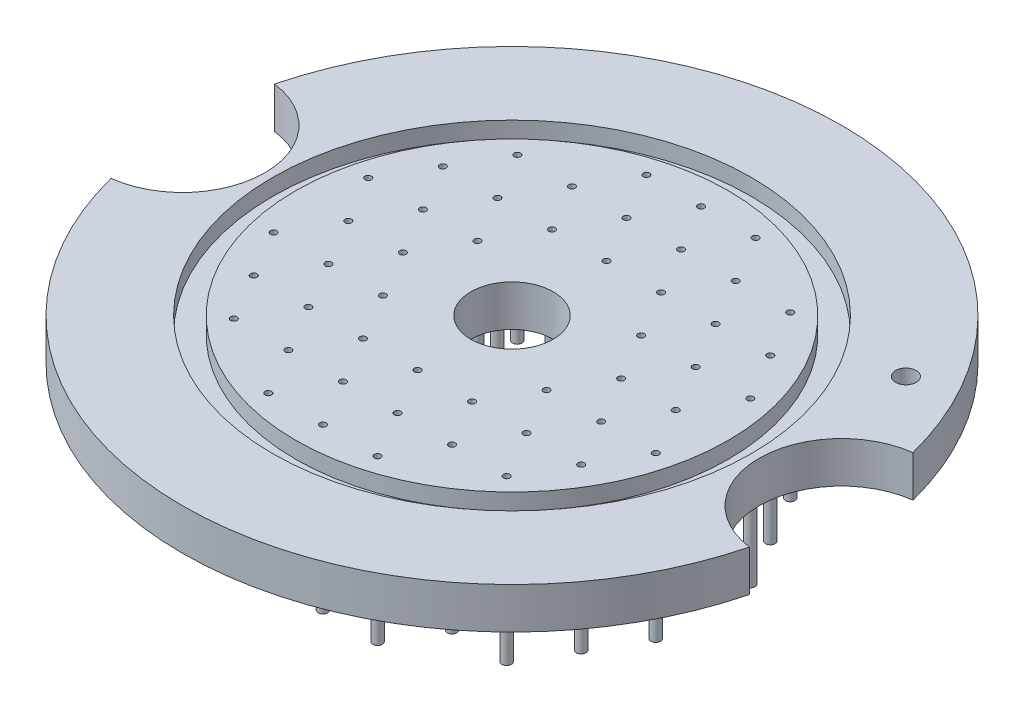
SolidWorks part; units mm, degrees
ref_plane "Front Plane" through (0, 0, 0) normal (0, 0, 1) x (1, 0, 0)
ref_plane "Top Plane" through (0, 0, 0) normal (0, 1, 0) x (1, 0, 0)
ref_plane "Right Plane" through (0, 0, 0) normal (1, 0, 0) x (0, 0, -1)
sketch "Sketch1" plane through (0, 0, 0) normal (0, 0, 1) x (1, 0, 0)
  line L0 (-33.3375, 6.35) -> (-33.3375, 3.81)
  line L1 (0, 0) -> (-50.8, 0)
  line L2 (0, 0) -> (0, 6.35)
  line L3 (0, 6.35) -> (-33.3375, 6.35)
  line L4 (-50.8, 0) -> (-50.8, 6.35)
  line L5 (-33.3375, 3.81) -> (-36.8935, 3.81)
  line L6 (-36.8935, 3.81) -> (-36.8935, 6.35)
  line L7 (-36.8935, 6.35) -> (-50.8, 6.35)
  dimension "D1" = 6.35
  dimension "D2" = 50.8
  dimension "D3" = 2.54
  dimension "D4" = 3.556
  dimension "D5" = 33.3375
revolve "Revolve1" add sketch "Sketch1" angle 360 about L2
hole_wizard "1/2 (0.5) Diameter Hole1" positions "Sketch2" profile "Sketch3" hole size "1/2" standard "ANSI Inch" end condition through all
sketch "Sketch2" plane through (0, 6.35, 0) normal (0, 1, 0) x (1, 0, 0)
  point P0 (0, 0)
sketch "Sketch3" plane through (0, 6.35, 0) normal (1, 0, 0) x (0, 0, 1)
  line L0 (0, 0) -> (0, 6.35)
  line L1 (0, 6.35) -> (6.35, 6.35)
  line L2 (6.35, 6.35) -> (6.35, 0)
  line L5 (6.35, 0) -> (0, 0)
  line L11 (0, -6.35) -> (0, 107.95) construction
  dimension "Thru Hole Dia." = 12.7
  dimension "Thru Hole Depth" = 6.35
hole_wizard "1 (1) Diameter Hole1" positions "Sketch4" profile "Sketch5" hole size "1" standard "ANSI Inch" end condition through all
sketch "Sketch4" plane through (0, 6.35, 0) normal (0, 1, 0) x (1, 0, 0)
  circle A0 centre (0, 0) radius 50.8 construction
  point P0 (50.8, 0)
  point P4 (-50.8, 0)
sketch "Sketch5" plane through (50.8, 6.35, 0) normal (1, 0, 0) x (0, 0, 1)
  line L0 (0, 0) -> (0, 6.35)
  line L1 (0, 6.35) -> (12.7, 6.35)
  line L2 (12.7, 6.35) -> (12.7, 0)
  line L5 (12.7, 0) -> (0, 0)
  line L11 (0, -6.35) -> (0, 107.95) construction
  dimension "Thru Hole Dia." = 25.4
  dimension "Thru Hole Depth" = 6.35
hole_wizard "1/8 (0.125) Diameter Hole1" positions "Sketch8" profile "Sketch7" hole size "1/8" standard "ANSI Inch" end condition through all
sketch "Sketch8" plane through (0, 6.35, 0) normal (0, 1, 0) x (1, 0, 0)
  line L0 (0, 0) -> (38.4948, 22.225) construction
  line L2 (0, 0) -> (46.6204, 0) construction
  point P0 (38.4948, 22.225)
  dimension "D1" = 30
  dimension "D2" = 44.45
sketch "Sketch7" plane through (38.4948, 6.35, -22.225) normal (1, 0, 0) x (0, 0, 1)
  line L0 (0, 0) -> (0, 6.35)
  line L1 (0, 6.35) -> (1.5875, 6.35)
  line L2 (1.5875, 6.35) -> (1.5875, 0)
  line L5 (1.5875, 0) -> (0, 0)
  line L11 (0, -6.35) -> (0, 107.95) construction
  dimension "Thru Hole Dia." = 3.175
  dimension "Thru Hole Depth" = 6.35
sketch "Sketch9" plane through (0, 0, 0) normal (0, -1, 0) x (1, 0, 0)
  line L0 (0, 14.573) -> (4.2069, 21.8596) construction
  line L1 (4.2069, 21.8596) -> (8.4138, 29.1461) construction
  line L2 (8.4138, 29.1461) -> (0, 29.1461) construction
  line L3 (0, 29.1461) -> (-8.4137, 29.1461) construction
  line L4 (-8.4137, 29.1461) -> (-12.6206, 21.8596) construction
  line L5 (-12.6206, 21.8596) -> (-8.4137, 14.573) construction
  line L6 (-8.4137, 14.573) -> (0, 14.573) construction
  line L7 (0, 14.573) -> (-4.2069, 21.8596) construction
  line L8 (-4.2069, 21.8596) -> (-8.4137, 14.573) construction
  line L9 (-12.6206, 21.8596) -> (-4.2069, 21.8596) construction
  line L10 (-4.2069, 21.8596) -> (-8.4137, 29.1461) construction
  line L11 (0, 29.1461) -> (-4.2069, 21.8596) construction
  line L12 (-4.2069, 21.8596) -> (4.2069, 21.8596) construction
  line L13 (4.2069, 21.8596) -> (0, 29.1461) construction
  line L14 (-8.4137, 14.573) -> (0, 0) construction
  line L15 (0, 0) -> (0, 14.573) construction
  circle A0 centre (0, 0) radius 12.7 construction
  circle A1 centre (0, 0) radius 31.75 construction
  circle A2 centre (8.4138, 29.1461) radius 0.7366
  circle A3 centre (8.4138, 29.1461) radius 0.4953
  circle A4 centre (0, 29.1461) radius 0.4953
  circle A5 centre (0, 29.1461) radius 0.7366
  circle A8 centre (-8.4137, 29.1461) radius 0.4953 [skipped]
  circle A9 centre (-8.4137, 29.1461) radius 0.7366 [skipped]
  circle A10 centre (4.2069, 21.8596) radius 0.4953
  circle A11 centre (4.2069, 21.8596) radius 0.7366
  circle A12 centre (0, 14.573) radius 0.4953
  circle A13 centre (0, 14.573) radius 0.7366
  circle A14 centre (-8.4138, 14.573) radius 0.4953
  circle A15 centre (-8.4138, 14.573) radius 0.7366
  circle A16 centre (-12.6206, 21.8596) radius 0.4953
  circle A17 centre (-12.6206, 21.8596) radius 0.7366
  circle A18 centre (-8.4138, 29.1461) radius 0.4953
  circle A19 centre (-8.4138, 29.1461) radius 0.7366
  circle A20 centre (-4.2069, 21.8596) radius 0.7366
  circle A21 centre (-4.2069, 21.8596) radius 0.4953
  point P4 (0, 14.573)
  point P5 (0, 29.1461)
  point P6 (-4.2069, 21.8596)
  point P7 (4.2069, 21.8596)
  point P8 (8.4138, 29.1461)
  point P9 (-8.4137, 29.1461)
  point P10 (-12.6206, 21.8596)
  point P11 (-8.4137, 14.573)
  point P46 (-4.2069, 21.8596)
  dimension "D1" = 25.4
  dimension "D8" = 1.4732
  dimension "D9" = 0.9906
  dimension "D2" = 19.05
  dimension "D3" = 8.4137
  dimension "D4" = 8.4137
  dimension "D5" = 8.4137
  dimension "D6" = 8.4137
  dimension "D10" = 3
  dimension "D12" = 2
  dimension "D11" = 6
extrude "Boss-Extrude1" add sketch "Sketch9" along normal blind 18.415
ref_axis "Axis2" through (0, 7.5565, 0) along (0, -1, 0)
extrude "Cut-Extrude1" cut sketch "Sketch9<2>" against normal through all contours A3 | A10 | A21 | A4 | A14 | A12 | A16 | A18
sketch "Sketch9<2>" plane through (0, 0, 0) normal (0, -1, 0) x (1, 0, 0) same geometry as "Sketch9"
pattern_circular "CirPattern4" count 6 over 360 about axis through (0, 7.5565, 0) along (0, -1, 0) of "Boss-Extrude1", "Cut-Extrude1"
equation "\"D4@Sketch9\"=\"D3@Sketch9\""
equation "\"D5@Sketch9\"=\"D3@Sketch9\""
equation "\"D6@Sketch9\"=\"D3@Sketch9\""
